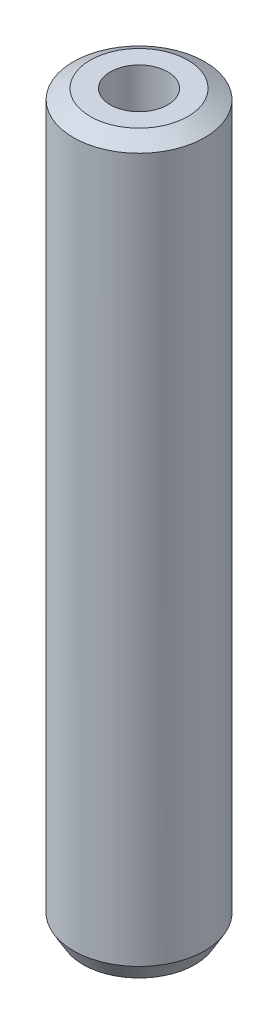
SolidWorks part; units mm, degrees
ref_plane "Front Plane" through (0, 0, 0) normal (0, 0, 1) x (1, 0, 0)
ref_plane "Top Plane" through (0, 0, 0) normal (0, 1, 0) x (1, 0, 0)
ref_plane "Right Plane" through (0, 0, 0) normal (1, 0, 0) x (0, 0, -1)
sketch "Sketch1" plane through (0, 0, 0) normal (0, 1, 0) x (1, 0, 0)
  circle A0 centre (0, 0) radius 35
  dimension "SHAFT_OD" = 70
extrude "Boss-Extrude1" add sketch "Sketch1" along normal blind 389.1431
sketch "Sketch2" plane through (0, 0, 0) normal (0, 1, 0) x (1, 0, 0)
  circle A0 centre (0, 0) radius 15.2707
  dimension "BORE_D" = 30.5414
extrude "Cut-Extrude1" cut sketch "Sketch2" along normal through all
chamfer "Chamfer1" distance 5.2043 angle 60 2 edges at (0, 389.1431, 35) (0, 0, 35) first distance on face at (0, 389.1431, 35) first distance on face at (0, 0, 15.2707)
